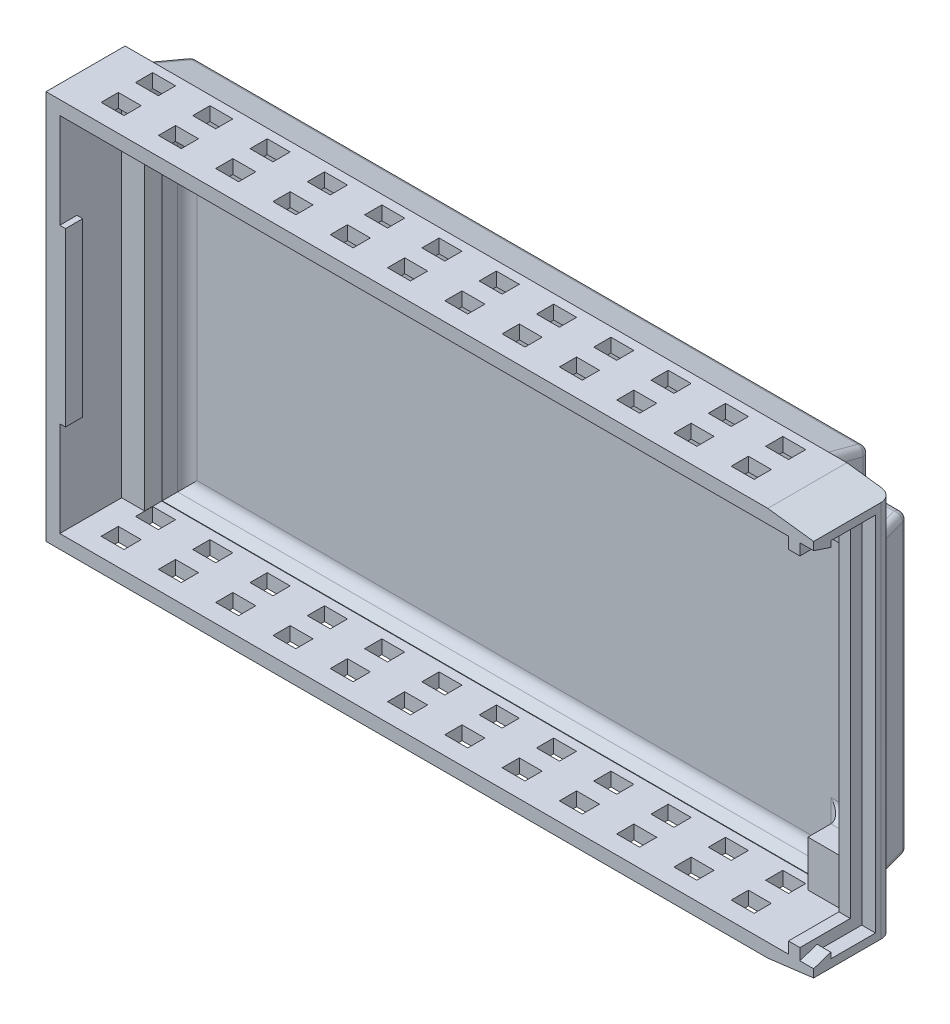
SolidWorks part; units mm, degrees
ref_plane "Front Plane" through (0, 0, 0) normal (0, 0, 1) x (1, 0, 0)
ref_plane "Top Plane" through (0, 0, 0) normal (0, 1, 0) x (1, 0, 0)
ref_plane "Right Plane" through (0, 0, 0) normal (1, 0, 0) x (0, 0, -1)
sketch "Sketch1" plane through (0, 0, 0) normal (0, 0, 1) x (1, 0, 0)
  line L1 (-33.5, -17) -> (33.5, -17)
  line L2 (-33.5, -17) -> (-33.5, 17)
  line L3 (-33.5, 17) -> (33.5, 17)
  line L4 (33.5, -17) -> (33.5, 17)
  line L5 (-33.5, -17) -> (33.5, 17) construction
  line L6 (-33.5, 17) -> (33.5, -17) construction
  point P0 (0, 0)
  dimension "D1" = 34
  dimension "D2" = 67
extrude "Boss-Extrude1" add sketch "Sketch1" along normal blind 1.5
extrude "Extrude-Thin1" add sketch "Sketch1<2>" along normal blind 5.4 from surface thin starting at face at (0, 0, 1.5) thin type one direction reverse wall 1.2
sketch "Sketch1<2>" plane through (0, 0, 0) normal (0, 0, 1) x (1, 0, 0) same geometry as "Sketch1"
sketch "Sketch3" plane through (32.3, 0, 0) normal (-1, 0, 0) x (0, 0, 1)
  line L0 (6.9, -15.8) -> (1.5, -15.8) construction
  line L1 (1.5, -15.8) -> (1.5, 15.8) construction
  line L2 (6.9, 15.8) -> (1.5, 15.8) construction
  line L3 (6.9, -15.8) -> (1.5, -15.8)
  line L4 (1.5, -15.8) -> (1.5, 15.8)
  line L5 (6.9, 15.8) -> (1.5, 15.8)
sketch "Sketch2" plane through (32.3, 0, 0) normal (-1, 0, 0) x (0, 0, 1)
  line L4 (1.5, 15.8) -> (1.5, -15.8)
  line L5 (1.5, -15.8) -> (6.9, -15.8)
  line L6 (6.9, -15.8) -> (6.9, 15.8)
  line L7 (6.9, 15.8) -> (1.5, 15.8)
  line L8 (1.5, 15.8) -> (1.5, -15.8)
  line L9 (1.5, -15.8) -> (6.9, -15.8)
  line L10 (6.9, -15.8) -> (6.9, 15.8)
  line L11 (6.9, 15.8) -> (1.5, 15.8)
  dimension "D1" = 0
extrude "Cut-Extrude1" cut sketch "Sketch2" against normal through all
extrude "Extrude-Thin2" add sketch "Sketch3" along normal blind 1 thin thin type one direction reverse wall 1
sketch "Sketch4" plane through (0, 0, 1.5) normal (0, 0, 1) x (1, 0, 0)
  line L0 (31.3, 15.8) -> (-32.3, 15.8) construction
  line L1 (-30.3, 15.8) -> (31.3, 15.8)
  line L2 (-30.3, 15.8) -> (-30.3, -15.8)
  line L3 (-30.3, -15.8) -> (31.3, -15.8)
  line L4 (31.3, 15.8) -> (31.3, -15.8)
  line L5 (-32.3, -15.8) -> (31.3, -15.8) construction
  line L6 (-32.3, 15.8) -> (-32.3, -15.8) construction
  line L7 (31.3, 15.8) -> (31.3, -15.8) construction
  dimension "D1" = 2
extrude "Cut-Extrude2" cut sketch "Sketch4" against normal through all
sketch "Sketch5" plane through (0, 0, 0) normal (0, 0, -1) x (-1, 0, 0)
  line L0 (33.5, -17) -> (-33.5, -17) construction
  line L1 (31.5, -17) -> (-32.5, -17)
  line L2 (31.5, -17) -> (31.5, 17)
  line L3 (31.5, 17) -> (-32.5, 17)
  line L4 (-32.5, -17) -> (-32.5, 17)
  line L5 (-33.5, 17) -> (33.5, 17) construction
  line L6 (30.3, 15.8) -> (30.3, -15.8) construction
  line L7 (-31.3, -15.8) -> (-31.3, 15.8) construction
  dimension "D1" = 1.2
  dimension "D2" = 1.2
extrude "Boss-Extrude2" add sketch "Sketch5" along normal blind 3 draft 15 separate body
sketch "Sketch6" plane through (0, 0, -3) normal (0, 0, -1) x (-1, 0, 0)
  line L1 (-33.5, -17) -> (-28.5, -17)
  line L2 (-33.5, -17) -> (-33.5, -13)
  line L3 (-33.5, -13) -> (-28.5, -13)
  line L4 (-28.5, -17) -> (-28.5, -13)
  line L6 (-33.5, 17) -> (-28.5, 17)
  line L7 (-33.5, 17) -> (-33.5, 13)
  line L8 (-33.5, 13) -> (-28.5, 13)
  line L9 (-28.5, 17) -> (-28.5, 13)
  dimension "D1" = 4
  dimension "D2" = 5
extrude "Cut-Extrude3" cut sketch "Sketch6" against normal up to surface (3 mm away) up to face at (0.5, 0, 0)
sketch "Sketch7" plane through (0, 0, 0) normal (0, 0, 1) x (1, 0, 0)
  line L1 (31.3, -15.8) -> (27.3, -15.8)
  line L2 (31.3, -15.8) -> (31.3, -11.8)
  line L3 (31.3, -11.8) -> (27.3, -11.8)
  line L4 (27.3, -15.8) -> (27.3, -11.8)
  line L5 (31.3, 15.8) -> (27.3, 15.8)
  line L6 (31.3, 15.8) -> (31.3, 11.8)
  line L7 (31.3, 11.8) -> (27.3, 11.8)
  line L8 (27.3, 15.8) -> (27.3, 11.8)
  line L9 (28.5, 17) -> (28.5, 13) construction
  line L10 (28.5, 13) -> (32.5, 13) construction
  dimension "D1" = 1.2
  dimension "D2" = 1.2
shell "Shell1" thickness 1.2 removed face at (14.5, 0, 0)
combine bodies "Combine1" operation type add bodies to combine 105 107
extrude "Boss-Extrude3" add sketch "Sketch7" along normal blind 1.2
fillet "Fillet1" radius 0.6 16 edges at (30.0981, -13, -3) (31.6962, 0, -3) (30.0981, 13, -3) (28.5, 14.5981, -3) (-1.0981, 16.1962, -3) (-30.6962, 0, -3) (-1.0981, -16.1962, -3) (28.5, -14.5981, -3) (-31.0981, -16.5981, -1.5) (28.5, -16.5981, -1.5) (28.5, -13, -1.5) (32.0981, -13, -1.5) (32.0981, 13, -1.5) (28.5, 13, -1.5) (28.5, 16.5981, -1.5) (-31.0981, 16.5981, -1.5)
fillet "Fillet2" radius 1 8 edges at (-1.2377, -15.2754, -1.8) (-29.7754, 0, -1.8) (-1.2377, 15.2754, -1.8) (27.3, 13.5377, -1.8) (29.0377, 11.8, -1.8) (30.7754, 0, -1.8) (29.0377, -11.8, -1.8) (27.3, -13.5377, -1.8)
chamfer "Chamfer1" distance 4 distance2 0.5 2 edges at (33.5, 17, 3.45) (33.5, -17, 3.45) first distance on face at (-0.5034, 17, 2.3) first distance on face at (-0.5034, -17, 2.3)
fillet "Fillet4" radius 1 1 edges at (33.5, 0, 0)
sketch "Sketch8" plane through (0, -17, 0) normal (0, -1, 0) x (1, 0, 0)
  line L0 (-25.2863, 5.3069) -> (-25.2863, 3.8069)
  line L1 (-30.2863, 5.3069) -> (-28.2863, 5.3069)
  line L2 (-30.2863, 5.3069) -> (-30.2863, 3.8069)
  line L3 (-30.2863, 3.8069) -> (-28.2863, 3.8069)
  line L4 (-28.2863, 5.3069) -> (-28.2863, 3.8069)
  line L5 (-25.2863, 5.3069) -> (-23.2863, 5.3069)
  line L6 (-23.2863, 5.3069) -> (-23.2863, 3.8069)
  line L7 (-25.2863, 3.8069) -> (-23.2863, 3.8069)
  line L8 (-20.2863, 5.3069) -> (-20.2863, 3.8069)
  line L9 (-20.2863, 5.3069) -> (-18.2863, 5.3069)
  line L10 (-18.2863, 5.3069) -> (-18.2863, 3.8069)
  line L11 (-20.2863, 3.8069) -> (-18.2863, 3.8069)
  line L12 (-15.2863, 5.3069) -> (-15.2863, 3.8069)
  line L13 (-15.2863, 5.3069) -> (-13.2863, 5.3069)
  line L14 (-13.2863, 5.3069) -> (-13.2863, 3.8069)
  line L15 (-15.2863, 3.8069) -> (-13.2863, 3.8069)
  line L16 (-10.2863, 5.3069) -> (-10.2863, 3.8069)
  line L17 (-10.2863, 5.3069) -> (-8.2863, 5.3069)
  line L18 (-8.2863, 5.3069) -> (-8.2863, 3.8069)
  line L19 (-10.2863, 3.8069) -> (-8.2863, 3.8069)
  line L20 (-5.2863, 5.3069) -> (-5.2863, 3.8069)
  line L21 (-5.2863, 5.3069) -> (-3.2863, 5.3069)
  line L22 (-3.2863, 5.3069) -> (-3.2863, 3.8069)
  line L23 (-5.2863, 3.8069) -> (-3.2863, 3.8069)
  line L24 (-0.2863, 5.3069) -> (-0.2863, 3.8069)
  line L25 (-0.2863, 5.3069) -> (1.7137, 5.3069)
  line L26 (1.7137, 5.3069) -> (1.7137, 3.8069)
  line L27 (-0.2863, 3.8069) -> (1.7137, 3.8069)
  line L28 (4.7137, 5.3069) -> (4.7137, 3.8069)
  line L29 (4.7137, 5.3069) -> (6.7137, 5.3069)
  line L30 (6.7137, 5.3069) -> (6.7137, 3.8069)
  line L31 (4.7137, 3.8069) -> (6.7137, 3.8069)
  line L32 (9.7137, 5.3069) -> (9.7137, 3.8069)
  line L33 (9.7137, 5.3069) -> (11.7137, 5.3069)
  line L34 (11.7137, 5.3069) -> (11.7137, 3.8069)
  line L35 (9.7137, 3.8069) -> (11.7137, 3.8069)
  line L36 (14.7137, 5.3069) -> (14.7137, 3.8069)
  line L37 (14.7137, 5.3069) -> (16.7137, 5.3069)
  line L38 (16.7137, 5.3069) -> (16.7137, 3.8069)
  line L39 (14.7137, 3.8069) -> (16.7137, 3.8069)
  line L40 (19.7137, 5.3069) -> (19.7137, 3.8069)
  line L41 (19.7137, 5.3069) -> (21.7137, 5.3069)
  line L42 (21.7137, 5.3069) -> (21.7137, 3.8069)
  line L43 (19.7137, 3.8069) -> (21.7137, 3.8069)
  line L44 (24.7137, 5.3069) -> (24.7137, 3.8069)
  line L45 (24.7137, 5.3069) -> (26.7137, 5.3069)
  line L46 (26.7137, 5.3069) -> (26.7137, 3.8069)
  line L47 (24.7137, 3.8069) -> (26.7137, 3.8069)
  line L48 (-25.2863, 2.3069) -> (-25.2863, 0.8069)
  line L49 (-25.2863, 2.3069) -> (-23.2863, 2.3069)
  line L50 (-23.2863, 2.3069) -> (-23.2863, 0.8069)
  line L51 (-25.2863, 0.8069) -> (-23.2863, 0.8069)
  line L52 (-20.2863, 2.3069) -> (-20.2863, 0.8069)
  line L53 (-20.2863, 2.3069) -> (-18.2863, 2.3069)
  line L54 (-18.2863, 2.3069) -> (-18.2863, 0.8069)
  line L55 (-20.2863, 0.8069) -> (-18.2863, 0.8069)
  line L56 (-15.2863, 2.3069) -> (-15.2863, 0.8069)
  line L57 (-15.2863, 2.3069) -> (-13.2863, 2.3069)
  line L58 (-13.2863, 2.3069) -> (-13.2863, 0.8069)
  line L59 (-15.2863, 0.8069) -> (-13.2863, 0.8069)
  line L60 (-10.2863, 2.3069) -> (-10.2863, 0.8069)
  line L61 (-10.2863, 2.3069) -> (-8.2863, 2.3069)
  line L62 (-8.2863, 2.3069) -> (-8.2863, 0.8069)
  line L63 (-10.2863, 0.8069) -> (-8.2863, 0.8069)
  line L64 (-5.2863, 2.3069) -> (-5.2863, 0.8069)
  line L65 (-5.2863, 2.3069) -> (-3.2863, 2.3069)
  line L66 (-3.2863, 2.3069) -> (-3.2863, 0.8069)
  line L67 (-5.2863, 0.8069) -> (-3.2863, 0.8069)
  line L68 (-0.2863, 2.3069) -> (-0.2863, 0.8069)
  line L69 (-0.2863, 2.3069) -> (1.7137, 2.3069)
  line L70 (1.7137, 2.3069) -> (1.7137, 0.8069)
  line L71 (-0.2863, 0.8069) -> (1.7137, 0.8069)
  line L72 (4.7137, 2.3069) -> (4.7137, 0.8069)
  line L73 (4.7137, 2.3069) -> (6.7137, 2.3069)
  line L74 (6.7137, 2.3069) -> (6.7137, 0.8069)
  line L75 (4.7137, 0.8069) -> (6.7137, 0.8069)
  line L76 (9.7137, 2.3069) -> (9.7137, 0.8069)
  line L77 (9.7137, 2.3069) -> (11.7137, 2.3069)
  line L78 (11.7137, 2.3069) -> (11.7137, 0.8069)
  line L79 (9.7137, 0.8069) -> (11.7137, 0.8069)
  line L80 (14.7137, 2.3069) -> (14.7137, 0.8069)
  line L81 (14.7137, 2.3069) -> (16.7137, 2.3069)
  line L82 (16.7137, 2.3069) -> (16.7137, 0.8069)
  line L83 (14.7137, 0.8069) -> (16.7137, 0.8069)
  line L84 (19.7137, 2.3069) -> (19.7137, 0.8069)
  line L85 (19.7137, 2.3069) -> (21.7137, 2.3069)
  line L86 (21.7137, 2.3069) -> (21.7137, 0.8069)
  line L87 (19.7137, 0.8069) -> (21.7137, 0.8069)
  line L88 (24.7137, 2.3069) -> (24.7137, 0.8069)
  line L89 (24.7137, 2.3069) -> (26.7137, 2.3069)
  line L90 (26.7137, 2.3069) -> (26.7137, 0.8069)
  line L91 (24.7137, 0.8069) -> (26.7137, 0.8069)
  line L92 (-30.2863, 2.3069) -> (-30.2863, 0.8069)
  line L93 (-30.2863, 2.3069) -> (-28.2863, 2.3069)
  line L94 (-28.2863, 2.3069) -> (-28.2863, 0.8069)
  line L95 (-30.2863, 0.8069) -> (-28.2863, 0.8069)
  dimension "D1" = 1.5
  dimension "D2" = 2
  dimension "D3" = 12
  dimension "D4" = 2
extrude "Cut-Extrude4" cut sketch "Sketch8" against normal through all
sketch "Sketch10" plane through (0, 15.8, 0) normal (0, -1, 0) x (1, 0, 0)
  line L0 (33.5, 6.9) -> (33.5, 1.5) construction
  line L1 (32.3, 6.9) -> (33.5, 6.9)
  line L2 (32.3, 6.9) -> (32.3, 5.4)
  line L3 (32.3, 5.4) -> (33.5, 5.4)
  line L4 (33.5, 6.9) -> (33.5, 5.4)
  dimension "D1" = 1.5
extrude "Boss-Extrude4" add sketch "Sketch10" along normal blind 0.5
mirror "Mirror5" about plane through (0, 0, 0) normal (0, 1, 0) of "Boss-Extrude4"
chamfer "Chamfer2" distance 0.5 distance2 1.5 2 edges at (32.9, 15.3, 6.9) (32.9, -15.3, 6.9) first distance on face at (17.5444, 0, 6.9)
sketch "Sketch11" plane through (-32.3, 0, 0) normal (1, 0, 0) x (0, 0, -1)
  line L0 (-6.9, 15.8) -> (-6.9, -15.8) construction
  line L1 (-6.9, -7.5) -> (-5.4, -7.5)
  line L2 (-6.9, -7.5) -> (-6.9, 7.5)
  line L3 (-6.9, 7.5) -> (-5.4, 7.5)
  line L4 (-5.4, -7.5) -> (-5.4, 7.5)
  point P6 (-6.9, 0)
  point P7 (-6.9, 0)
  dimension "D1" = 15
  dimension "D2" = 1.5
extrude "Boss-Extrude5" add sketch "Sketch11" along normal blind 0.5
